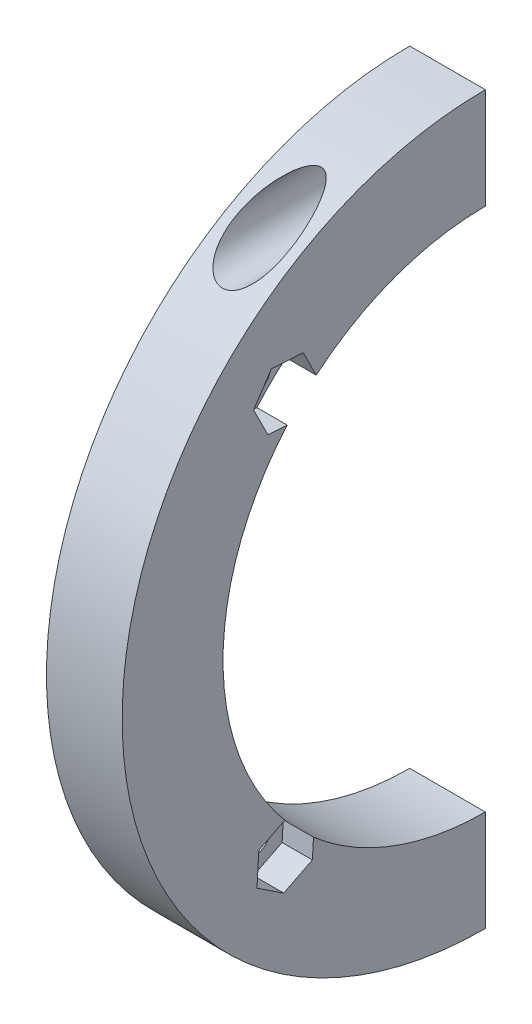
SolidWorks part; units mm, degrees
ref_plane "Front Plane" through (0, 0, 0) normal (0, 0, 1) x (1, 0, 0)
ref_plane "Top Plane" through (0, 0, 0) normal (0, 1, 0) x (1, 0, 0)
ref_plane "Right Plane" through (0, 0, 0) normal (1, 0, 0) x (0, 0, -1)
sketch "Sketch1" plane through (0, 0, 0) normal (1, 0, 0) x (0, 0, -1)
  line L0 (0, 48.5907) -> (0, -40.0599)
  line L1 (0, 0) -> (-19.799, 19.799)
  circle A0 centre (0, 0) radius 36
  circle A1 centre (0, 0) radius 26
  circle A2 centre (-19.799, 19.799) radius 1.5
  circle A6 centre (19.799, 19.799) radius 1.5
  circle A7 centre (19.799, -19.799) radius 1.5
  circle A8 centre (-19.799, -19.799) radius 1.5
  point P17 (4.1496, 9.1596)
  point P18 (0, 0)
  dimension "D1" = 72
  dimension "D2" = 52
  dimension "D5" = 3
  dimension "D3" = 45
  dimension "D4" = 28
  dimension "D6" = 4
extrude "Boss-Extrude1" add sketch "Sketch1" along normal blind 3.75 and the other way blind 3.75 contours A1 L0 A0 region at (0, 31, 0.805)
sketch "Sketch3" plane through (0, 0, 0) normal (0, 0, -1) x (-1, 0, 0)
  line L1 (3.75, 26) -> (-3.75, 26) construction
  circle A0 centre (0, 31) radius 1.5
  dimension "D1" = 3
  dimension "D2" = 5
extrude "Cut-Extrude1" cut sketch "Sketch3" against normal blind 25.5
mirror "Mirror1" about plane through (0, 0, 0) normal (0, 1, 0) of "Cut-Extrude1"
ref_plane "Plane1" through (0, 0, 30) normal (0, 0, -1) x (-1, 0, 0)
sketch "Sketch4" plane through (0, 0, 30) normal (0, 0, -1) x (-1, 0, 0)
  circle A2 centre (0, 31) radius 2.75
  circle A3 centre (0, 31) radius 2.75
  dimension "D1" = 1.25
extrude "Cut-Extrude2" cut sketch "Sketch4" along normal blind 25
sketch "Sketch5" plane through (0, 0, 30) normal (0, 0, -1) x (-1, 0, 0)
  line L0 (-3.75, -26) -> (-3.75, -36) construction
  line L1 (2.75, -32.5877) -> (2.75, -29.4123)
  line L2 (2.75, -29.4123) -> (0, -27.8246)
  line L3 (0, -27.8246) -> (-2.75, -29.4123)
  line L4 (-2.75, -29.4123) -> (-2.75, -32.5877)
  line L5 (-2.75, -32.5877) -> (0, -34.1754)
  line L6 (0, -34.1754) -> (2.75, -32.5877)
  circle A1 centre (0, -31) radius 2.75 construction
  dimension "D1" = 5.5
  dimension "D2" = 0
extrude "Cut-Extrude3" cut sketch "Sketch5" along normal blind 25
sketch "Sketch6" plane through (3.75, 0, 0) normal (1, 0, 0) x (0, 0, -1)
  line L18 (-22.4522, -18.0544) -> (-22.6365, -21.2244)
  line L19 (-18.0544, 22.4522) -> (-21.2244, 22.6365)
  line L20 (-21.2244, 22.6365) -> (-22.9691, 19.9833)
  line L21 (-22.9691, 19.9833) -> (-21.5436, 17.1458)
  line L22 (-21.5436, 17.1458) -> (-18.3735, 16.9615)
  line L23 (-18.3735, 16.9615) -> (-16.6289, 19.6147)
  line L24 (-16.6289, 19.6147) -> (-18.0544, 22.4522)
  line L25 (-22.6365, -21.2244) -> (-19.9833, -22.9691)
  line L26 (-19.9833, -22.9691) -> (-17.1458, -21.5436)
  line L27 (-17.1458, -21.5436) -> (-16.9615, -18.3735)
  line L28 (-16.9615, -18.3735) -> (-19.6147, -16.6289)
  line L29 (-19.6147, -16.6289) -> (-22.4522, -18.0544)
  line L30 (18.0544, -22.4522) -> (21.2244, -22.6365)
  line L31 (21.2244, -22.6365) -> (22.9691, -19.9833)
  line L32 (22.9691, -19.9833) -> (21.5436, -17.1458)
  line L33 (21.5436, -17.1458) -> (18.3735, -16.9615)
  line L34 (18.3735, -16.9615) -> (16.6289, -19.6147)
  line L35 (16.6289, -19.6147) -> (18.0544, -22.4522)
  line L36 (22.4522, 18.0544) -> (22.6365, 21.2244)
  line L37 (22.6365, 21.2244) -> (19.9833, 22.9691)
  line L38 (19.9833, 22.9691) -> (17.1458, 21.5436)
  line L39 (17.1458, 21.5436) -> (16.9615, 18.3735)
  line L40 (16.9615, 18.3735) -> (19.6147, 16.6289)
  line L41 (19.6147, 16.6289) -> (22.4522, 18.0544)
  circle A1 centre (-19.799, 19.799) radius 2.75 construction
  point P32 (0, 0)
  dimension "D1" = 4
  dimension "D3" = 5.5
extrude "Cut-Extrude4" cut sketch "Sketch6" against normal blind 3
